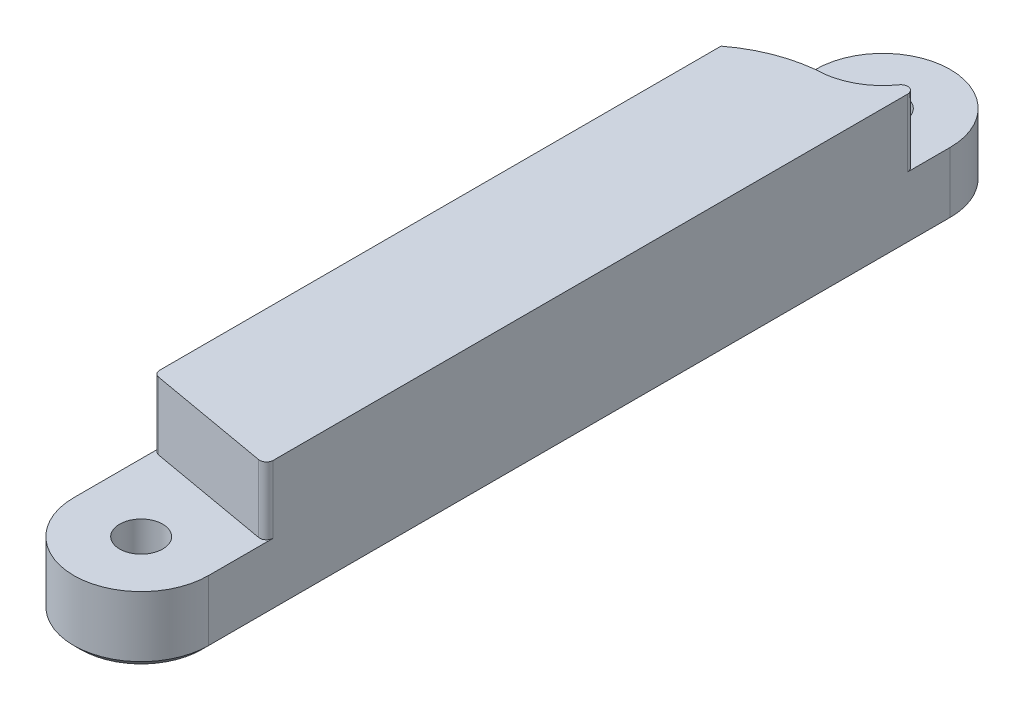
SolidWorks part; units mm, degrees
ref_plane "Front Plane" through (0, 0, 0) normal (0, 0, 1) x (1, 0, 0)
ref_plane "Top Plane" through (0, 0, 0) normal (0, 1, 0) x (1, 0, 0)
ref_plane "Right Plane" through (0, 0, 0) normal (1, 0, 0) x (0, 0, -1)
other "Configuration Table"
sketch "complete_sketch" plane through (0, 0, 0) normal (0, 1, 0) x (1, 0, 0)
  line L0 (0, 0) -> (0, 55) construction
  line L1 (-5, 0) -> (-5, 55)
  line L2 (5, 0) -> (5, 55)
  line L3 (5, 4.1955) -> (-5, 5.9588)
  line L4 (-5, 5.9588) -> (-5, 52.7087)
  line L5 (5, 4.1955) -> (5, 52.7087)
  line L6 (-5, 47) -> (5, 47)
  arc A0 (-5, 0) -> (5, 0) centre (0, 0) ccw
  arc A1 (5, 55) -> (-5, 55) centre (0, 55) ccw
  circle A2 centre (0, 55) radius 1.6
  circle A3 centre (0, 0) radius 1.6
  circle A5 centre (0, 0) radius 5 construction
  circle A6 centre (0, 55) radius 5 construction
  point P3 (0, 27.5)
  dimension "D2" = 3.2
  dimension "D5" = 8
  dimension "D1" = 10
  dimension "D3" = 55
  dimension "D4" = 100
extrude "center_body" add sketch "complete_sketch" along normal blind 10 contours L6 L1 L3 L2 region at (0.035, 0, -26.0355)
extrude "connector_body" add sketch "Sketch1<3>" along normal blind 5 contours L1 A0 L2 L3 A3 | L1 L2 A1 A2 region at (-4.8516, 0, -2.9794) region at (0, 0, -52.8722)
sketch "Sketch1<3>" plane through (0, 0, 0) normal (0, 1, 0) x (1, 0, 0) same geometry as "complete_sketch"
sketch "Sketch1" plane through (0, 5, 0) normal (0, 1, 0) x (1, 0, 0)
  line L0 (-5, 47) -> (5, 47)
  line L1 (5, 47) -> (5, 55)
  line L3 (-5, 5.9588) -> (-5, 47) construction
  line L4 (-5, 47) -> (-5, 55) construction
  line L5 (-5, 48) -> (-5, 47)
  circle A0 centre (0, 55) radius 5 construction
  arc A1 (5, 55) -> (0, 50) centre (0, 55) cw
  arc A3 (0, 50) -> (-5, 48) centre (1.0767, 40.0581) ccw
  dimension "D1" = 10
  dimension "D2" = 10
  dimension "D3" = 1
extrude "mech_lock_left" add sketch "Sketch1" along normal blind 5
sketch "Sketch2" [suppressed] plane through (0, 5, 0) normal (0, 1, 0) x (1, 0, 0)
  line L0 (5, 47) -> (-5, 47)
  line L1 (-5, 47) -> (-5, 55)
  line L2 (5, 47) -> (5, 48)
  line L3 (5, 47) -> (5, 55) construction
  circle A0 centre (0, 55) radius 5 construction
  arc A1 (-5, 55) -> (0, 50) centre (0, 55) ccw
  arc A3 (0, 50) -> (5, 48) centre (-1.0767, 40.0581) cw
  dimension "D1" = 10
  dimension "D2" = 10
  dimension "D3" = 1
extrude "mech_lock_right" [suppressed] add sketch "Sketch2" along normal blind 5
fillet "dulling_fillet_general" radius 0.5 2 edges at (5, 7.5, -4.1955) (-5, 7.5, -5.9588)
chamfer "elephantsfoot_compensation" distance 0.5 angle 45 6 edges at (0, 0, -53.4) (0, 0, 1.6) (0, 0, 5) (0, 0, -60) (5, 0, -27.5) (-5, 0, -27.5)
fillet "dulling_fillet_left" radius 0.5 1 edges at (5, 7.5, -55)
fillet "dulling_fillet_right" [suppressed] radius 0.5
